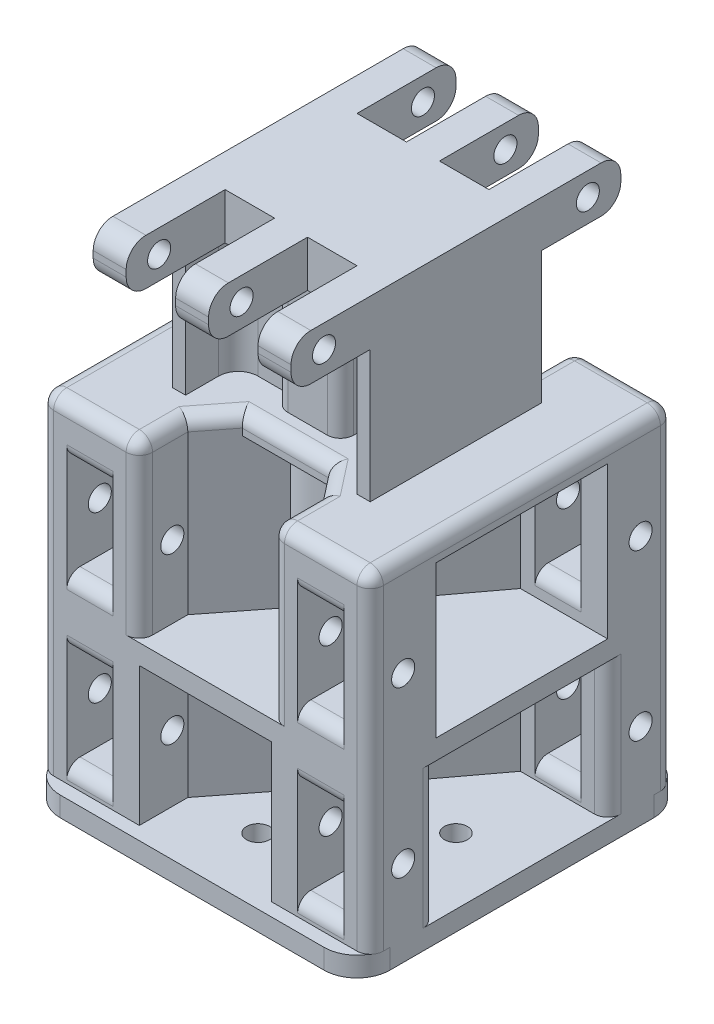
SolidWorks part; units mm, degrees
ref_plane "Front Plane" through (0, 0, 0) normal (0, 0, 1) x (1, 0, 0)
ref_plane "Top Plane" through (0, 0, 0) normal (0, 1, 0) x (1, 0, 0)
ref_plane "Right Plane" through (0, 0, 0) normal (1, 0, 0) x (0, 0, -1)
sketch "Sketch1" plane through (0, 0, 0) normal (0, 1, 0) x (1, 0, 0)
  line L1 (-20, 25) -> (20, 25)
  line L2 (-25, 20) -> (-25, -20)
  line L3 (-20, -25) -> (20, -25)
  line L4 (25, 20) -> (25, -20)
  line L5 (-25, 25) -> (25, -25) construction
  line L6 (-25, -25) -> (25, 25) construction
  arc A0 (-25, -20) -> (-20, -25) centre (-20, -20) ccw
  arc A1 (20, -25) -> (25, -20) centre (20, -20) ccw
  arc A2 (20, 25) -> (25, 20) centre (20, 20) cw
  arc A3 (-20, 25) -> (-25, 20) centre (-20, 20) ccw
  point P0 (0, 0)
  dimension "D3" = 5
  dimension "D1" = 50
  dimension "D2" = 50
extrude "Boss-Extrude1" add sketch "Sketch1" along normal blind 3
sketch "Sketch2" plane through (0, 3, 0) normal (0, 1, 0) x (1, 0, 0)
  line L0 (20, 25) -> (-20, 25) construction
  line L1 (-25, 23) -> (-10, 23)
  line L2 (-25, 23) -> (-25, 13)
  line L3 (-25, 13) -> (-10, 13)
  line L4 (-10, 23) -> (-10, 13)
  dimension "D1" = 10
  dimension "D2" = 15
  dimension "D3" = 2
extrude "Boss-Extrude2" add sketch "Sketch2" along normal blind 50
sketch "Sketch3" plane through (0, 0, -23) normal (0, 0, -1) x (-1, 0, 0)
  line L0 (25, 53) -> (25, 3) construction
  line L1 (14, 45.5) -> (21, 45.5)
  line L2 (14, 45.5) -> (14, 30.5)
  line L3 (14, 30.5) -> (21, 30.5)
  line L4 (21, 45.5) -> (21, 30.5)
  line L5 (14, 20.5) -> (21, 20.5)
  line L6 (14, 20.5) -> (14, 5.5)
  line L7 (14, 5.5) -> (21, 5.5)
  line L8 (21, 20.5) -> (21, 5.5)
  line L9 (10, 53) -> (10, 3) construction
  line L10 (14, 30.5) -> (14, 20.5) construction
  line L11 (21, 30.5) -> (21, 20.5) construction
  line L12 (10, 3) -> (24, 3) construction
  dimension "D1" = 4
  dimension "D2" = 4
  dimension "D3" = 15
  dimension "D4" = 15
  dimension "D5" = 2.5
  dimension "D6" = 10
extrude "Cut-Extrude1" cut sketch "Sketch3" against normal blind 10
sketch "Sketch4" plane through (-25, 0, 0) normal (-1, 0, 0) x (0, 0, 1)
  line L0 (-18, 12.9994) -> (-18, 2.9994) construction
  line L2 (-18, 37.9994) -> (-18, 12.9994) construction
  line L3 (-18, 2.9994) -> (-18, 0) construction
  line L4 (-20, 0) -> (20, 0) construction
  line L5 (-18, 53) -> (-18, 37.9994) construction
  line L6 (-23, 53) -> (-13, 53) construction
  circle A0 centre (-18, 37.9994) radius 1.75
  circle A1 centre (-18, 12.9994) radius 1.75
  dimension "D1" = 3.5
  dimension "D2" = 3.5
  dimension "D3" = 10
  dimension "D4" = 25
extrude "Cut-Extrude2" cut sketch "Sketch4" against normal blind 15
mirror "Mirror4" about plane through (0, 0, 0) normal (1, 0, 0) of "Cut-Extrude2", "Cut-Extrude1", "Boss-Extrude2", "Boss-Extrude1"
sketch "Sketch5" plane through (0, 3, 0) normal (0, 1, 0) x (1, 0, 0)
  line L0 (-12.62, -14.1372) -> (-5.6013, -5.1536)
  line L1 (-12.62, -14.1372) -> (-10.256, -15.9842)
  line L2 (10.256, 15.9842) -> (12.62, 14.1372)
  line L3 (-10.256, -15.9842) -> (-3.1731, -6.9185)
  line L4 (-12.62, -14.1372) -> (12.62, 14.1372) construction
  line L5 (10.256, 15.9842) -> (-10.256, -15.9842) construction
  line L6 (12.6173, -13.713) -> (5.7762, -4.9568)
  line L7 (12.6173, -13.713) -> (10.2533, -15.56)
  line L8 (-10.2533, 15.56) -> (-12.6173, 13.713)
  line L9 (10.2533, -15.56) -> (3.4122, -6.8038)
  line L10 (12.6173, -13.713) -> (-12.6173, 13.713) construction
  line L11 (-10.2533, 15.56) -> (10.2533, -15.56) construction
  line L12 (0, 0) -> (0, 10.4542) construction
  line L13 (-3.4122, 6.8038) -> (-10.2533, 15.56)
  line L14 (-5.7762, 4.9568) -> (-12.6173, 13.713)
  line L18 (5.7677, 4.9667) -> (12.62, 14.1372)
  line L20 (3.4238, 6.7979) -> (10.256, 15.9842)
  arc A0 (-5.7762, 4.9568) -> (-5.6013, -5.1536) centre (0, 0) ccw
  arc A1 (3.4238, 6.7979) -> (-3.4122, 6.8038) centre (0, 0) ccw
  arc A2 (5.7762, -4.9568) -> (5.7677, 4.9667) centre (0, 0) ccw
  arc A3 (-3.1731, -6.9185) -> (3.4122, -6.8038) centre (0, 0) ccw
  dimension "D1" = 38
  dimension "D2" = 38
  dimension "D3" = 3
  dimension "D4" = 3
  dimension "D5" = 3
extrude "Boss-Extrude3" add sketch "Sketch5" along normal blind 21
sketch "Sketch6" plane through (0, 3, 0) normal (0, 1, 0) x (1, 0, 0)
  line L0 (0, 0) -> (0, 15) construction
  line L1 (0, 0) -> (15, 0) construction
  line L3 (0, -15) -> (0, 0) construction
  line L4 (0, 0) -> (-15, 0) construction
  circle A0 centre (-15, 0) radius 1.75
  circle A1 centre (0, 15) radius 1.75
  circle A2 centre (15, 0) radius 1.75
  circle A3 centre (0, -15) radius 1.75
  dimension "D5" = 3.5
  dimension "D6" = 3.5
  dimension "D7" = 3.5
  dimension "D8" = 3.5
  dimension "D1" = 15
  dimension "D2" = 15
  dimension "D3" = 15
  dimension "D4" = 15
extrude "Cut-Extrude3" cut sketch "Sketch6" against normal blind 21
sketch "Sketch7" plane through (0, 24, 0) normal (0, 1, 0) x (1, 0, 0)
  line L1 (-23, -23) -> (23, -23)
  line L2 (-25, -21) -> (-25, 21)
  line L3 (-23, 23) -> (23, 23)
  line L4 (25, -21) -> (25, 21)
  line L5 (-25, -23) -> (25, 23) construction
  line L6 (-25, 23) -> (25, -23) construction
  arc A0 (-23, -23) -> (-25, -21) centre (-23, -21) cw
  arc A1 (23, -23) -> (25, -21) centre (23, -21) ccw
  arc A2 (23, 23) -> (25, 21) centre (23, 21) cw
  arc A3 (-25, 21) -> (-23, 23) centre (-23, 21) cw
  point P0 (0, 0)
  dimension "D1" = 2
extrude "Boss-Extrude4" add sketch "Sketch7" along normal blind 3
sketch "Sketch8" plane through (0, 27, 0) normal (0, 1, 0) x (1, 0, 0)
  line L0 (-12.62, -14.1372) -> (-5.6013, -5.1536)
  line L1 (-12.62, -14.1372) -> (-10.256, -15.9842)
  line L2 (10.256, 15.9842) -> (12.62, 14.1372)
  line L3 (-10.256, -15.9842) -> (-3.1731, -6.9185)
  line L4 (-12.62, -14.1372) -> (12.62, 14.1372) construction
  line L5 (10.256, 15.9842) -> (-10.256, -15.9842) construction
  line L6 (12.6173, -13.713) -> (5.7762, -4.9568)
  line L7 (12.6173, -13.713) -> (10.2533, -15.56)
  line L8 (-10.2533, 15.56) -> (-12.6173, 13.713)
  line L9 (10.2533, -15.56) -> (3.4122, -6.8038)
  line L10 (12.6173, -13.713) -> (-12.6173, 13.713) construction
  line L11 (-10.2533, 15.56) -> (10.2533, -15.56) construction
  line L12 (0, 0) -> (0, 6.5806) construction
  line L13 (-3.4122, 6.8038) -> (-10.2533, 15.56)
  line L14 (-5.7762, 4.9568) -> (-12.6173, 13.713)
  line L15 (5.7677, 4.9667) -> (12.62, 14.1372)
  line L16 (3.4238, 6.7979) -> (10.256, 15.9842)
  arc A0 (-5.7762, 4.9568) -> (-5.6013, -5.1536) centre (0, 0) ccw
  arc A1 (3.4238, 6.7979) -> (-3.4122, 6.8038) centre (0, 0) ccw
  arc A2 (5.7762, -4.9568) -> (5.7677, 4.9667) centre (0, 0) ccw
  arc A3 (-3.1731, -6.9185) -> (3.4122, -6.8038) centre (0, 0) ccw
  dimension "D1" = 38
  dimension "D2" = 38
  dimension "D3" = 3
  dimension "D4" = 3
  dimension "D5" = 3
extrude "Boss-Extrude5" add sketch "Sketch8" along normal blind 23
sketch "Sketch9" plane through (0, 50, 0) normal (0, 1, 0) x (1, 0, 0)
  line L0 (10, 23) -> (10, 15.64)
  line L1 (-23, -23) -> (-10, -23)
  line L2 (-25, -21) -> (-25, 21)
  line L3 (-23, 23) -> (-10, 23)
  line L4 (25, -21) -> (25, 21)
  line L5 (-25, -23) -> (25, 23) construction
  line L6 (-25, 23) -> (25, -23) construction
  line L7 (10, 15.64) -> (6.7119, 11.219)
  line L8 (10, 15.64) -> (3.4238, 6.7979) construction
  line L9 (6.7119, 11.219) -> (-6.8617, 11.219)
  line L10 (-3.4122, 6.8038) -> (-10, 15.2358) construction
  line L11 (-6.8617, 11.219) -> (-10, 15.2358)
  line L12 (10, 23) -> (23, 23)
  line L13 (-10, 15.2358) -> (-10, 23)
  line L14 (-27.5, 0) -> (27.5, 0) construction
  line L15 (-10, -15.6565) -> (-10, -23)
  line L16 (-6.3774, -11.0198) -> (-10, -15.6565)
  line L17 (10, -15.2358) -> (6.7061, -11.0198)
  line L18 (6.7061, -11.0198) -> (-6.3774, -11.0198)
  line L19 (10, -23) -> (10, -15.2358)
  line L20 (10, -13) -> (10, -23) construction
  line L21 (3.4122, -6.8038) -> (10, -15.2358) construction
  line L22 (-10, -13) -> (-10, -23) construction
  line L23 (-10, -15.6565) -> (-3.1731, -6.9185) construction
  line L24 (10, -23) -> (23, -23)
  arc A0 (-23, -23) -> (-25, -21) centre (-23, -21) cw
  arc A1 (23, -23) -> (25, -21) centre (23, -21) ccw
  arc A2 (23, 23) -> (25, 21) centre (23, 21) cw
  arc A3 (-25, 21) -> (-23, 23) centre (-23, 21) cw
  point P0 (0, 0)
  dimension "D1" = 2
extrude "Boss-Extrude6" add sketch "Sketch9" along normal blind 3
fillet "Fillet1" radius 2 44 edges at (-25, 28, 23) (-10, 40, 23) (25, 28, -23) (10, 40, -23) (25, 28, 23) (10, 40, 23) (-17.5, 30.5, 23) (-17.5, 45.5, 23) (-17.5, 30.5, 13) (-17.5, 45.5, 13) (-17.5, 5.5, 23) (-17.5, 20.5, 23) (-17.5, 5.5, 13) (-17.5, 20.5, 13) (17.5, 30.5, -23) (17.5, 45.5, -23) (17.5, 30.5, -13) (17.5, 45.5, -13) (17.5, 5.5, -23) (17.5, 20.5, -23) (17.5, 5.5, -13) (17.5, 20.5, -13) (17.5, 45.5, 13) (17.5, 30.5, 13) (17.5, 30.5, 23) (17.5, 45.5, 23) (17.5, 20.5, 13) (17.5, 5.5, 13) (17.5, 5.5, 23) (17.5, 20.5, 23) (-25, 28, -23) (-10, 40, -23) (-25, 13.5, 13) (-25, 13.5, -13) (25, 13.5, -13) (25, 13.5, 13) (-17.5, 45.5, -13) (-17.5, 30.5, -13) (-17.5, 30.5, -23) (-17.5, 45.5, -23) (-17.5, 20.5, -13) (-17.5, 5.5, -13) (-17.5, 5.5, -23) (-17.5, 20.5, -23)
fillet "Fillet2" radius 2 24 edges at (10, 53, 18.1179) (10, 53, -18.32) (-10, 53, 18.3283) (-10, 53, -18.1179) (-8.1887, 53, 13.3382) (0.1643, 53, 11.0198) (8.353, 53, 13.1278) (8.356, 53, -13.4295) (-0.0749, 53, -11.219) (-8.4308, 53, -13.2274) (-17.5, 53, 23) (17.5, 53, 23) (-17.5, 53, -23) (-25, 53, 0) (25, 53, 0) (17.5, 53, -23) (-24.4142, 53, -22.4142) (-10.5858, 53, -22.4142) (10.5858, 53, -22.4142) (10.5858, 53, 22.4142) (-24.4142, 53, 22.4142) (24.4142, 53, -22.4142) (24.4142, 53, 22.4142) (-10.5858, 53, 22.4142)
sketch "Sketch10" plane through (0, 53, 0) normal (0, 1, 0) x (1, 0, 0)
  line L0 (-5, 5) -> (5, 5) construction
  line L1 (-13, 5) -> (-5, 5)
  line L2 (-15, 3) -> (-15, -3)
  line L3 (-13, -5) -> (-5, -5)
  line L4 (15, 2.1696) -> (15, -3)
  line L5 (5, -5) -> (5, 5) construction
  line L6 (-5, 5) -> (-5, -5) construction
  line L7 (-5, -5) -> (5, -5) construction
  line L8 (-3, -7.5) -> (3, -7.5)
  line L10 (-3, 7.4998) -> (3, 7.4998)
  line L12 (0, 5) -> (0, 0) construction
  line L13 (0, 0) -> (5, 0) construction
  line L14 (-5, 5.4998) -> (-5, 5)
  line L16 (5, 5.5) -> (5, 5)
  line L17 (5, -5) -> (5, -5.5)
  line L18 (-5, -5.5) -> (-5, -5)
  line L19 (5, 5) -> (13, 5)
  line L20 (5, -5) -> (13, -5)
  line L22 (-13, 5) -> (-13, 13)
  line L23 (-13, 13) -> (-15, 13)
  line L24 (-15, 13) -> (-15, 3)
  line L25 (-15, -3) -> (-15, -13)
  line L26 (-15, -13) -> (-13, -13)
  line L27 (-13, -13) -> (-13, -5)
  line L28 (15, 2.1696) -> (15, 13)
  line L29 (15, 13) -> (13, 13)
  line L30 (13, 13) -> (13, 5)
  line L31 (15, -3) -> (15, -13)
  line L32 (15, -13) -> (13, -13)
  line L33 (13, -13) -> (13, -5)
  line L34 (-13, 5) -> (-13, -5) construction
  line L35 (13, 5) -> (13, -5) construction
  arc A0 (3, -7.5) -> (5, -5.5) centre (3, -5.5) ccw
  arc A1 (-3, -7.5) -> (-5, -5.5) centre (-3, -5.5) cw
  arc A8 (3, 7.4998) -> (5, 5.5) centre (3, 5.4998) cw
  arc A9 (-5, 5.4998) -> (-3, 7.4998) centre (-3, 5.4998) cw
  point P0 (0, 0)
  point P8 (0, 0)
  point P21 (-5, -7.5)
  point P37 (15, -5)
  point P42 (5, 7.5)
  point P45 (-5, 7.5)
  point P48 (-15, -5)
  point P51 (-15, 5)
  dimension "D5" = 2
  dimension "D1" = 10
  dimension "D2" = 10
  dimension "D3" = 30
  dimension "D4" = 15
  dimension "D6" = 2
  dimension "D7" = 8
  dimension "D8" = 8
  dimension "D9" = 9.9999
  dimension "D10" = 8
  dimension "D11" = 8
  dimension "D12" = 8
  dimension "D13" = 8
extrude "Boss-Extrude7" add sketch "Sketch10" along normal blind 20
sketch "Sketch13" plane through (0, 73, 0) normal (0, 1, 0) x (1, 0, 0)
  line L0 (20, 25) -> (-20, 25) construction
  line L1 (-15, -25) -> (15, -25)
  line L2 (-15, -25) -> (-15, 25)
  line L3 (-15, 25) -> (15, 25)
  line L4 (15, -25) -> (15, 25)
  line L5 (-15, -25) -> (15, 25) construction
  line L6 (-15, 25) -> (15, -25) construction
  point P0 (0, 0)
extrude "Boss-Extrude8" add sketch "Sketch13" along normal blind 7
fillet "Fillet3" radius 3 4 edges at (0, 73, -25) (0, 80, -25) (0, 80, 25) (0, 73, 25)
sketch "Sketch14" plane through (0, 80, 0) normal (0, 1, 0) x (1, 0, 0)
  line L0 (15, 25) -> (-15, 25) construction
  line L1 (-10, 25) -> (-2.5, 25)
  line L2 (-10, 25) -> (-10, 10)
  line L3 (-10, 10) -> (-2.5, 10)
  line L4 (-2.5, 25) -> (-2.5, 10)
  line L5 (-15, -25) -> (15, -25) construction
  line L6 (2.5, 10) -> (10, 10)
  line L7 (2.5, 10) -> (2.5, 25)
  line L8 (2.5, 25) -> (10, 25)
  line L9 (10, 10) -> (10, 25)
  line L10 (-10, -10) -> (-2.5, -10)
  line L11 (-10, -10) -> (-10, -25)
  line L12 (-10, -25) -> (-2.5, -25)
  line L13 (-2.5, -10) -> (-2.5, -25)
  line L14 (-10, 10) -> (-10, -10) construction
  line L15 (2.5, -10) -> (10, -10)
  line L16 (2.5, -10) -> (2.5, -25)
  line L17 (2.5, -25) -> (10, -25)
  line L18 (10, -10) -> (10, -25)
  line L19 (-2.5, 10) -> (-2.5, -10) construction
  line L20 (2.5, 10) -> (2.5, -10) construction
  line L21 (10, 10) -> (10, -10) construction
  line L22 (2.5, -10) -> (-2.5, -10) construction
  line L23 (-2.5, 10) -> (2.5, 10) construction
  line L24 (-15, 22) -> (-15, -22) construction
  line L25 (15, -22) -> (15, 22) construction
  dimension "D1" = 5
  dimension "D2" = 5
  dimension "D3" = 5
  dimension "D4" = 7.5
  dimension "D5" = 7.5
  dimension "D6" = 15
  dimension "D7" = 15
extrude "Cut-Extrude4" cut sketch "Sketch14" against normal blind 7
sketch "Sketch15" plane through (-15, 0, 0) normal (-1, 0, 0) x (0, 0, 1)
  line L0 (0, 80) -> (0, 76.5) construction
  line L1 (-22, 80) -> (22, 80) construction
  line L2 (0, 76.5) -> (-20, 76.5) construction
  line L3 (-20, 76.5) -> (-25, 76.5) construction
  line L4 (-25, 77) -> (-25, 76) construction
  line L5 (0, 76.5) -> (20, 76.5) construction
  circle A0 centre (-20, 76.5) radius 1.75
  circle A1 centre (20, 76.5) radius 1.75
  dimension "D1" = 3.5
  dimension "D4" = 3.5
  dimension "D2" = 20
  dimension "D3" = 20
extrude "Cut-Extrude5" cut sketch "Sketch15" against normal through all
fillet "Fillet4" radius 3 4 edges at (13, 63, -5) (-13, 63, -5) (13, 63, 5) (-13, 63, 5)
